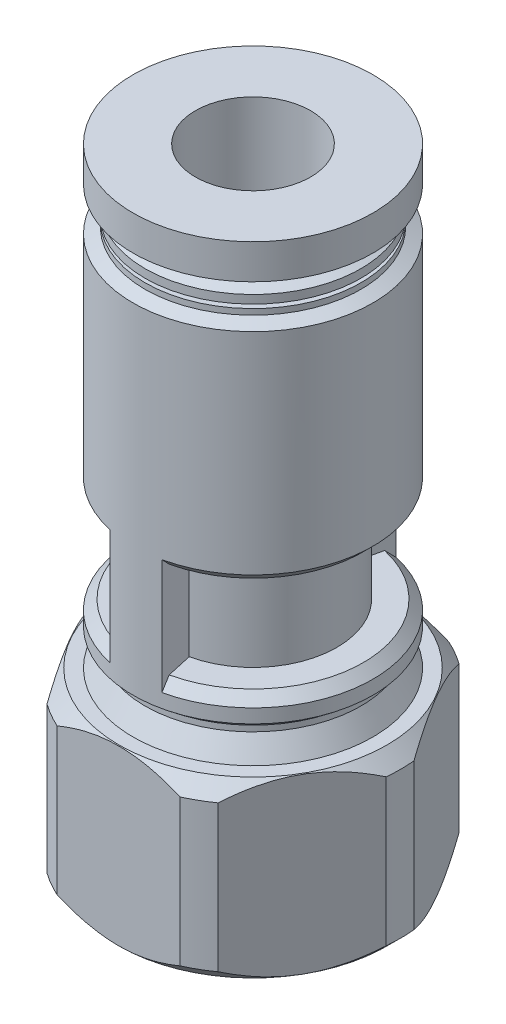
SolidWorks part; units mm, degrees
ref_plane "Front Plane" through (0, 0, 0) normal (0, 0, 1) x (1, 0, 0)
ref_plane "Top Plane" through (0, 0, 0) normal (0, 1, 0) x (1, 0, 0)
ref_plane "Right Plane" through (0, 0, 0) normal (1, 0, 0) x (0, 0, -1)
ref_plane "Plane1" through (0, 0, 0) normal (0, 0, 1) x (1, 0, 0)
sketch "Sketch1" plane through (0, 0, 0) normal (0, 0, 1) x (1, 0, 0)
  line L0 (0, 0) -> (-7, 0)
  line L1 (-7, 0) -> (-7.7, 0.7)
  line L2 (-7.7, 0.7) -> (-7.7, 8.325)
  line L3 (-7.7, 8.325) -> (-6.975, 9.05)
  line L4 (-6.975, 9.05) -> (-6.25, 9.05)
  line L5 (-6.25, 9.05) -> (-5.625, 10.136)
  line L6 (-5.625, 10.136) -> (-5.625, 10.436)
  line L7 (-5.625, 10.436) -> (-6.25, 10.936)
  line L8 (-6.25, 10.936) -> (-6.25, 11.66)
  line L9 (-6.25, 11.66) -> (-5.75, 12.16)
  line L10 (-5.75, 12.16) -> (-4.375, 12.16)
  line L11 (-4.375, 12.16) -> (-4.375, 17.16)
  line L12 (-4.375, 17.16) -> (-5.75, 17.16)
  line L13 (-5.75, 17.16) -> (-6.25, 17.66)
  line L14 (-6.25, 17.66) -> (-6.25, 28.642)
  line L15 (-6.25, 28.642) -> (-5.625, 28.942)
  line L16 (-5.625, 28.942) -> (-5.625, 29.242)
  line L17 (-5.625, 29.242) -> (-5, 29.242)
  line L18 (-5, 29.242) -> (-5, 29.442)
  line L19 (-5, 29.442) -> (-5.625, 29.442)
  line L20 (-5.625, 29.442) -> (-5.625, 29.8775)
  line L21 (-5.625, 29.8775) -> (-5, 30.166)
  line L22 (-5, 30.166) -> (-3.6, 30.166)
  line L23 (-3.6, 30.166) -> (-3.6, 30.89)
  line L24 (-3.6, 30.89) -> (-6.25, 30.89)
  line L25 (-6.25, 30.89) -> (-6.25, 32.7)
  line L26 (-6.25, 32.7) -> (0, 32.7)
  line L27 (0, 32.7) -> (0, 0)
  line L28 (0, 32.7) -> (0, 0) construction
revolve "Revolve1" add sketch "Sketch1" angle 360 about L28 reverse direction yes
ref_plane "Plane2" through (0, 0, 0) normal (0, 0, 1) x (1, 0, 0)
sketch "Sketch2" plane through (0, 0, 0) normal (0, 0, 1) x (1, 0, 0)
  line L0 (0, -3.5) -> (-2.0095, -3.5)
  line L1 (-2.0095, -3.5) -> (-2.5, -3.0095)
  line L2 (-2.5, -3.0095) -> (-2.5, -0.5)
  line L3 (-2.5, -0.5) -> (-4.2, -0.5)
  line L4 (-4.2, -0.5) -> (-4.2, 0)
  line L5 (-4.2, 0) -> (0, 0)
  line L6 (0, 0) -> (0, -3.5)
  line L7 (0, 0) -> (0, -3.5) construction
revolve "Revolve2" add sketch "Sketch2" angle 360 about L7 reverse direction yes
cosmetic thread "Cosmetic Thread1" parameters "D2"=4.11
ref_plane "Plane3" through (0, 0, 0) normal (0, 0, 1) x (1, 0, 0)
sketch "Sketch3" plane through (0, 0, 0) normal (0, 0, 1) x (1, 0, 0)
  line L0 (0, -3.5) -> (-1.25, -3.5)
  line L1 (-1.25, -3.5) -> (-1.25, 1)
  line L2 (-1.25, 1) -> (-3, 1)
  line L3 (-3, 1) -> (-3, 32.7)
  line L4 (-3, 32.7) -> (0, 32.7)
  line L5 (0, 32.7) -> (0, -3.5)
  line L6 (0, 32.7) -> (0, -3.5) construction
revolve "Cut-Revolve1" cut sketch "Sketch3" angle 360 about L6 reverse direction yes
ref_plane "Plane4" through (0, 0, 0) normal (0, 1, 0) x (-1, 0, 0)
sketch "Sketch4" plane through (0, 0, 0) normal (0, 1, 0) x (-1, 0, 0)
  line L0 (14, -14) -> (14, 14)
  line L1 (14, 14) -> (-14, 14)
  line L2 (-14, 14) -> (-14, -14)
  line L3 (-14, -14) -> (14, -14)
  line L4 (8.0829, 0) -> (4.0415, 7)
  line L5 (4.0415, 7) -> (-4.0415, 7)
  line L6 (-4.0415, 7) -> (-8.0829, 0)
  line L7 (-8.0829, 0) -> (-4.0415, -7)
  line L8 (-4.0415, -7) -> (4.0415, -7)
  line L9 (4.0415, -7) -> (8.0829, 0)
extrude "Cut-Extrude1" cut sketch "Sketch4" along normal blind 9.05
ref_plane "Plane5" through (0, 0, 0) normal (1, 0, 0) x (0, 0, -1)
sketch "Sketch5" plane through (0, 0, 0) normal (1, 0, 0) x (0, 0, -1)
  line L0 (3.75, 11.66) -> (6.25, 11.66)
  line L1 (6.25, 11.66) -> (6.25, 17.66)
  line L2 (6.25, 17.66) -> (3.75, 17.66)
  line L3 (3.75, 17.66) -> (3.75, 11.66)
  line L4 (0, 11.66) -> (0, 17.66) construction
revolve "Revolve3" add sketch "Sketch5" angle 12.5 about L4 other way angle 12.5
ref_plane "Plane6" through (0, 0, 0) normal (1, 0, 0) x (0, 0, -1)
sketch "Sketch6" plane through (0, 0, 0) normal (1, 0, 0) x (0, 0, -1)
  line L0 (-6.25, 11.66) -> (-3.75, 11.66)
  line L1 (-3.75, 11.66) -> (-3.75, 17.66)
  line L2 (-3.75, 17.66) -> (-6.25, 17.66)
  line L3 (-6.25, 17.66) -> (-6.25, 11.66)
  line L4 (0, 17.66) -> (0, 11.66) construction
revolve "Revolve4" add sketch "Sketch6" angle 12.5 about L4 other way angle 12.5
sketch "Sketch7" plane through (0, -3.5, 0) normal (0, -1, 0) x (1, 0, 0)
  circle A0 centre (0, 0) radius 1.5875
  dimension "D1" = 3.175
extrude "Cut-Extrude2" cut sketch "Sketch7" against normal through all
